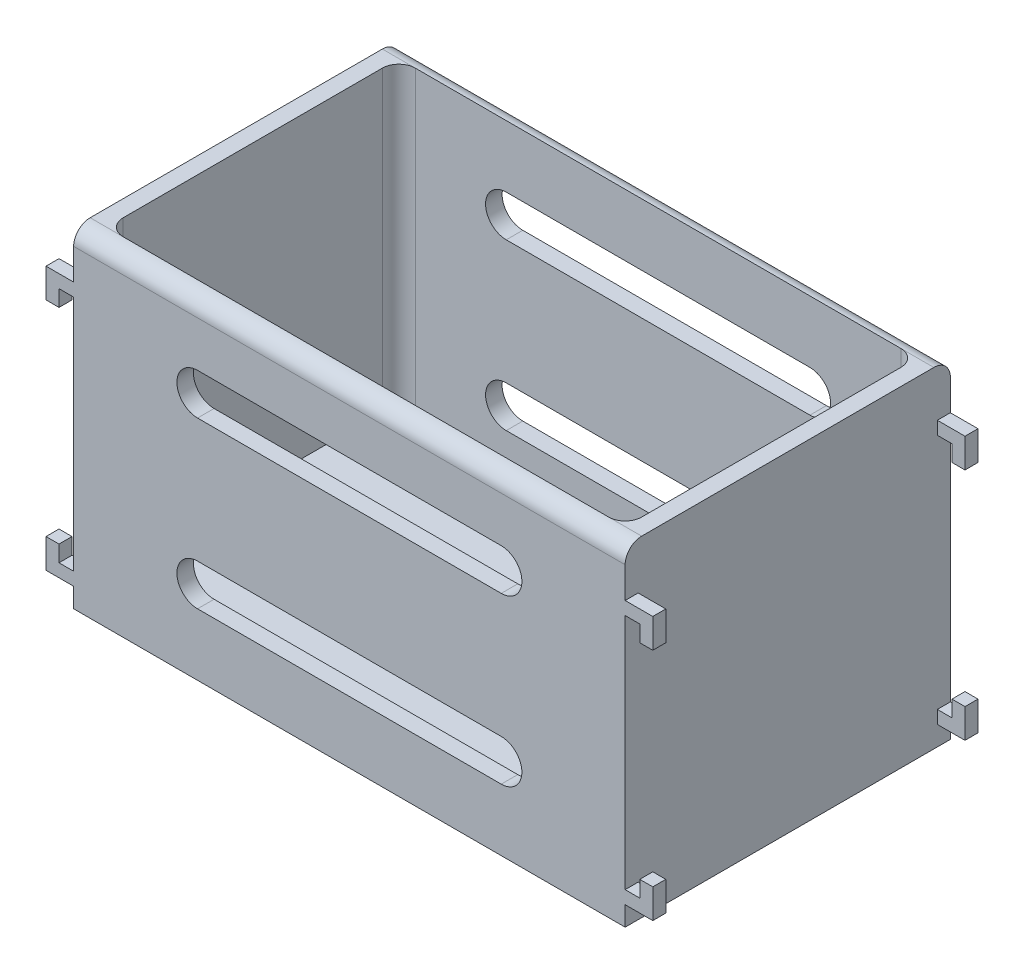
SolidWorks part; units mm, degrees
ref_plane "Front Plane" through (0, 0, 0) normal (0, 0, 1) x (1, 0, 0)
ref_plane "Top Plane" through (0, 0, 0) normal (0, 1, 0) x (1, 0, 0)
ref_plane "Right Plane" through (0, 0, 0) normal (1, 0, 0) x (0, 0, -1)
sketch "Sketch1" plane through (0, 0, 0) normal (0, 1, 0) x (1, 0, 0)
  line L0 (39.855, -22.46) -> (39.855, 22.46)
  line L1 (42.395, -25) -> (-42.395, -25)
  line L2 (42.395, -25) -> (42.395, 25)
  line L3 (42.395, 25) -> (-42.395, 25)
  line L4 (-42.395, -25) -> (-42.395, 25)
  line L5 (42.395, -25) -> (-42.395, 25) construction
  line L6 (42.395, 25) -> (-42.395, -25) construction
  line L7 (39.855, 22.46) -> (-39.855, 22.46)
  line L8 (-39.855, -22.46) -> (-39.855, 22.46)
  line L9 (39.855, -22.46) -> (-39.855, -22.46)
  line L11 (42.395, -25) -> (-42.395, -25)
  line L12 (42.395, -25) -> (42.395, 25)
  line L13 (42.395, 25) -> (-42.395, 25)
  line L14 (-42.395, -25) -> (-42.395, 25)
  line L15 (42.395, -25) -> (-42.395, 25) construction
  line L16 (42.395, 25) -> (-42.395, -25) construction
  line L17 (39.855, -22.46) -> (-39.855, -22.46)
  line L18 (39.855, -22.46) -> (39.855, 22.46)
  line L19 (39.855, 22.46) -> (-39.855, 22.46)
  line L20 (-39.855, -22.46) -> (-39.855, 22.46)
  line L21 (39.855, -22.46) -> (-39.855, 22.46) construction
  line L22 (39.855, 22.46) -> (-39.855, -22.46) construction
  point P0 (0, 0)
  point P10 (0, 0)
  point P11 (0, 0)
  dimension "D1" = 50
  dimension "D2" = 84.7901
  dimension "D3" = 2.54
extrude "Boss-Extrude1" add sketch "Sketch1" along normal blind 5 contours L0 L7 L8 L9
sketch "Sketch3" plane through (0, 0, 0) normal (0, -1, 0) x (1, 0, 0)
  line L1 (-42.395, 25) -> (42.395, 25)
  line L2 (-42.395, 25) -> (-42.395, -25)
  line L3 (-42.395, -25) -> (42.395, -25)
  line L4 (42.395, 25) -> (42.395, -25)
  line L5 (-39.855, -22.46) -> (39.855, -22.46)
  line L6 (-39.855, -22.46) -> (-39.855, 22.46)
  line L7 (-39.855, 22.46) -> (39.855, 22.46)
  line L8 (39.855, -22.46) -> (39.855, 22.46)
extrude "Boss-Extrude2" add sketch "Sketch3" against normal blind 50.8 separate body
sketch "Sketch5" plane through (0, 5, 0) normal (0, 1, 0) x (1, 0, 0)
  text T0 "MSW Robotics" font "Century Gothic" height 6.35
  point P6 (0, 0)
extrude "Cut-Extrude1" cut sketch "Sketch5" against normal blind 2.5
sketch "Sketch6" plane through (0, 0, 0) normal (0, -1, 0) x (1, 0, 0)
  line L2 (0, 0) -> (0, 28.9678) construction
  circle A0 centre (-33.545, 0) radius 2.5
  circle A1 centre (33.545, 0) radius 2.5
  dimension "D2" = 5
extrude "Cut-Extrude2" cut sketch "Sketch6" against normal up to surface (5 mm away) up to face at (-28.5133, 5, 2.3559)
sketch "Sketch7" plane through (0, 5, 0) normal (0, 1, 0) x (1, 0, 0)
  circle A0 centre (-33.545, 0) radius 3.81
  dimension "D1" = 7.62
sketch "Sketch8" plane through (0, 0, 25) normal (0, 0, 1) x (1, 0, 0)
  line L0 (-23.345, 38.1) -> (23.345, 38.1) construction
  line L1 (42.395, 50.8) -> (-42.395, 50.8) construction
  line L2 (-42.395, 50.8) -> (-42.395, 0) construction
  line L3 (-23.345, 41.275) -> (23.345, 41.275)
  line L4 (42.395, 50.8) -> (42.395, 0) construction
  line L5 (-42.395, 25.4) -> (42.395, 25.4) construction
  line L6 (-23.345, 34.925) -> (23.345, 34.925)
  line L7 (0, 50.8) -> (0, 0) construction
  line L8 (-23.345, 12.7) -> (23.345, 12.7) construction
  line L9 (-23.345, 15.875) -> (23.345, 15.875)
  line L10 (-23.345, 9.525) -> (23.345, 9.525)
  line L11 (42.395, 0) -> (-42.395, 0) construction
  arc A0 (-23.345, 41.275) -> (-23.345, 34.925) centre (-23.345, 38.1) ccw
  arc A1 (23.345, 34.925) -> (23.345, 41.275) centre (23.345, 38.1) ccw
  arc A2 (-23.345, 15.875) -> (-23.345, 9.525) centre (-23.345, 12.7) ccw
  arc A3 (23.345, 9.525) -> (23.345, 15.875) centre (23.345, 12.7) ccw
  point P6 (0, 38.1)
  point P10 (-23.345, 38.1)
  point P11 (23.345, 12.7)
  point P16 (-23.345, 12.7)
  point P20 (23.345, 38.1)
  point P22 (0, 12.7)
  dimension "D1" = 12.7
  dimension "D2" = 19.05
extrude "Cut-Extrude3" cut sketch "Sketch8" against normal up to surface (50 mm away) up to face at (0, 25.4, -25)
sketch "Sketch9" plane through (0, 50.8, 0) normal (0, 1, 0) x (1, 0, 0)
  line L1 (42.395, -25) -> (-42.395, -25) construction
  line L2 (39.855, 22.46) -> (39.855, 25)
  line L3 (-42.395, 25) -> (42.395, 25) construction
  line L4 (39.855, 25) -> (42.395, 25)
  line L5 (-42.395, 25) -> (-39.855, 25)
  line L6 (-42.395, 25) -> (-42.395, -25)
  line L7 (-42.395, -25) -> (-39.855, -25)
  line L8 (-39.855, 25) -> (-39.855, -25)
  line L10 (39.855, 25) -> (39.855, -25)
  line L12 (42.395, 25) -> (42.395, -25)
  line L13 (39.855, 25) -> (39.855, -25)
  line L14 (39.855, -25) -> (42.395, -25)
  line L15 (42.395, 25) -> (42.395, -25)
sketch "Sketch10" plane through (0, 50.8, 0) normal (0, 1, 0) x (1, 0, 0)
  line L1 (-42.395, 25) -> (-39.855, 25)
  line L2 (-42.395, 25) -> (-42.395, -25)
  line L3 (-42.395, -25) -> (-39.855, -25)
  line L4 (-39.855, 25) -> (-39.855, -25)
  line L5 (39.855, 25) -> (42.395, 25)
  line L6 (39.855, 25) -> (39.855, -25)
  line L7 (39.855, -25) -> (42.395, -25)
  line L8 (42.395, 25) -> (42.395, -25)
extrude "Boss-Extrude3" add sketch "Sketch10" against normal up to surface (50.8 mm away) up to face at (0, 0, 0)
sketch "Sketch12" plane through (0, 0, 25) normal (0, 0, 1) x (1, 0, 0)
  line L0 (-42.395, 5) -> (-42.395, 41.5)
  line L1 (-42.395, 0) -> (-42.395, 50.8) construction
  line L2 (-42.395, 23.25) -> (-54.5037, 23.25) construction
  line L3 (-42.395, 5) -> (-44.645, 5)
  line L4 (-44.645, 7.5) -> (-44.645, 5)
  line L5 (-46.645, 7.5) -> (-46.645, 3)
  line L10 (-42.395, 3) -> (-46.645, 3)
  line L11 (-44.645, 7.5) -> (-46.645, 7.5)
  line L12 (0, 0) -> (0, 58.6401) construction
  line L13 (-42.395, 5) -> (-42.395, 3)
  line L14 (-42.395, 41.5) -> (-44.645, 41.5)
  line L15 (-44.645, 39) -> (-44.645, 41.5)
  line L16 (-44.645, 39) -> (-46.645, 39)
  line L17 (-46.645, 39) -> (-46.645, 43.5)
  line L18 (-42.395, 43.5) -> (-46.645, 43.5)
  line L19 (-42.395, 41.5) -> (-42.395, 43.5)
  line L20 (42.395, 5) -> (44.645, 5)
  line L21 (44.645, 7.5) -> (44.645, 5)
  line L22 (44.645, 7.5) -> (46.645, 7.5)
  line L23 (46.645, 7.5) -> (46.645, 3)
  line L24 (42.395, 3) -> (46.645, 3)
  line L25 (42.395, 5) -> (42.395, 3)
  line L26 (42.395, 41.5) -> (42.395, 43.5)
  line L27 (42.395, 43.5) -> (46.645, 43.5)
  line L28 (46.645, 39) -> (46.645, 43.5)
  line L29 (44.645, 39) -> (46.645, 39)
  line L30 (44.645, 39) -> (44.645, 41.5)
  line L31 (42.395, 41.5) -> (44.645, 41.5)
  line M23 (42.395, 0) -> (42.395, 50.8)
  line M25 (-42.395, 50.8) -> (-42.395, 0)
  dimension "D1" = 36.5
  dimension "D2" = 2.25
  dimension "D3" = 2.5
  dimension "D4" = 2
extrude "Boss-Extrude4" add sketch "Sketch12" against normal blind 2 contours L18 L17 L16 L15 L14 M25 | L4 L11 L5 L10 L3 M25 | L31 L30 L29 L28 L27 M23 | L24 L23 L22 L21 L20 M23 region at (-44.9367, 41.6667, 25) region at (-44.9367, 4.8333, 25) region at (44.9367, 4.8333, 25) region at (44.9367, 41.6667, 25)
mirror "Mirror1" about plane through (0, 0, 0) normal (0, 0, 1) of "Boss-Extrude4"
fillet "Fillet1" radius 2.54 2 edges at (0, 50.8, 25) (0, 50.8, -25)
fillet "Fillet2" radius 2.54 4 edges at (-39.855, 27.9, -22.46) (-39.855, 27.9, 22.46) (39.855, 27.9, -22.46) (39.855, 27.9, 22.46)
